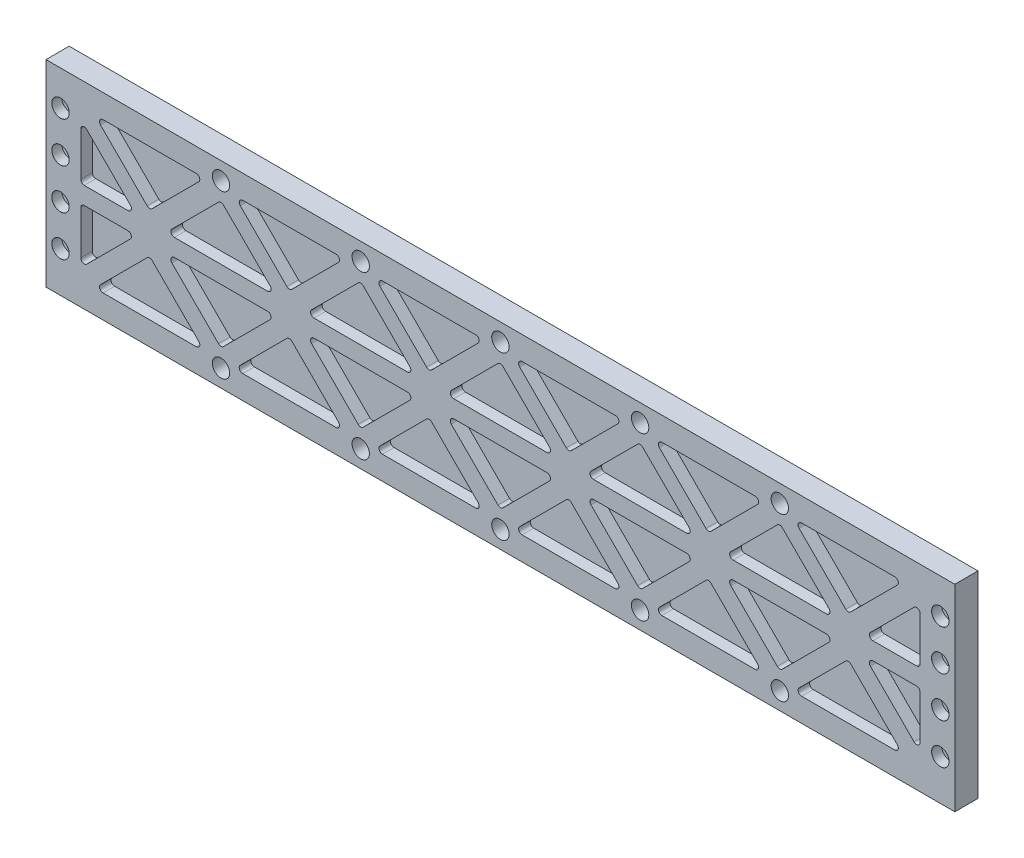
SolidWorks part; units mm, degrees
material "3.3547 (EN-AW 5083)"
ref_plane "Front Plane" through (0, 0, 0) normal (0, 0, 1) x (1, 0, 0)
ref_plane "Top Plane" through (0, 0, 0) normal (0, 1, 0) x (1, 0, 0)
ref_plane "Right Plane" through (0, 0, 0) normal (1, 0, 0) x (0, 0, -1)
sketch "Sketch1" plane through (0, 0, 0) normal (0, 0, 1) x (1, 0, 0)
  line L1 (392, -85) -> (-392, -85)
  line L2 (392, -85) -> (392, 85)
  line L3 (392, 85) -> (-392, 85)
  line L4 (-392, -85) -> (-392, 85)
  line L5 (392, -85) -> (-392, 85) construction
  line L6 (392, 85) -> (-392, -85) construction
  point P0 (0, 0)
  dimension "D1" = 784
  dimension "D2" = 170
extrude "Boss-Extrude1" add sketch "Sketch1" along normal blind 20
sketch "Sketch2" plane through (0, 0, 20) normal (0, 0, 1) x (1, 0, 0)
  line L0 (0, 0) -> (0, 85) construction
  line L1 (392, 85) -> (-392, 85) construction
  line L2 (-40.2574, 7.5) -> (40.2574, 7.5)
  line L3 (42.3787, 12.6213) -> (2.1213, 52.8787)
  line L5 (-2.1213, 52.8787) -> (-42.3787, 12.6213)
  line L7 (392, 0) -> (-392, 0) construction
  line L8 (392, -85) -> (392, 85) construction
  line L9 (-392, 85) -> (-392, -85) construction
  line L11 (-40.2574, -7.5) -> (40.2574, -7.5)
  line L12 (-2.1213, -52.8787) -> (-42.3787, -12.6213)
  line L13 (42.3787, -12.6213) -> (2.1213, -52.8787)
  arc A0 (2.1213, 52.8787) -> (-2.1213, 52.8787) centre (0, 50.7574) ccw
  arc A1 (-42.3787, 12.6213) -> (-40.2574, 7.5) centre (-40.2574, 10.5) ccw
  arc A2 (-40.2574, -7.5) -> (-42.3787, -12.6213) centre (-40.2574, -10.5) ccw
  arc A3 (-2.1213, -52.8787) -> (2.1213, -52.8787) centre (0, -50.7574) ccw
  arc A4 (42.3787, 12.6213) -> (40.2574, 7.5) centre (40.2574, 10.5) cw
  arc A5 (40.2574, -7.5) -> (42.3787, -12.6213) centre (40.2574, -10.5) cw
  point P30 (0, 55)
  point P33 (-47.5, 7.5)
  point P36 (-47.5, -7.5)
  point P39 (0, -55)
  point P42 (47.5, 7.5)
  point P45 (47.5, -7.5)
  dimension "D4" = 3
  dimension "D1" = 45
  dimension "D2" = 15
  dimension "D3" = 30
extrude "Cut-Extrude1" cut sketch "Sketch2" against normal blind 10
sketch "Sketch3" plane through (0, 0, 20) normal (0, 0, 1) x (1, 0, 0)
  line L1 (61.1066, 19.3492) -> (101.364, 59.6066)
  line L2 (99.2426, 64.7279) -> (18.7279, 64.7279)
  line L3 (16.6066, 59.6066) -> (56.864, 19.3492)
  line L7 (58.9853, 0) -> (58.9853, 21.4706) construction
  line L8 (16.6066, -59.6066) -> (56.864, -19.3492)
  line L9 (42.3787, 12.6213) -> (2.1213, 52.8787) construction
  line L10 (2.1213, -52.8787) -> (42.3787, -12.6213) construction
  line L11 (61.1066, -19.3492) -> (101.364, -59.6066)
  line L12 (58.9853, 0) -> (0, 0) construction
  line L13 (99.2426, -64.7279) -> (18.7279, -64.7279)
  line L15 (0, 50.7574) -> (0, 72.2279) construction
  arc A0 (101.364, 59.6066) -> (99.2426, 64.7279) centre (99.2426, 61.7279) ccw
  arc A1 (18.7279, 64.7279) -> (16.6066, 59.6066) centre (18.7279, 61.7279) ccw
  arc A2 (61.1066, 19.3492) -> (56.864, 19.3492) centre (58.9853, 21.4706) cw
  circle A3 centre (58.9853, 0) radius 21.4706 construction
  arc A5 (61.1066, -19.3492) -> (56.864, -19.3492) centre (58.9853, -21.4706) ccw
  arc A6 (18.7279, -64.7279) -> (16.6066, -59.6066) centre (18.7279, -61.7279) cw
  arc A7 (101.364, -59.6066) -> (99.2426, -64.7279) centre (99.2426, -61.7279) cw
  circle A8 centre (0, 72.2279) radius 21.4706 construction
  point P2 (40.2574, 10.5)
  point P13 (106.4853, 64.7279)
  point P16 (11.4853, 64.7279)
  point P22 (18.7279, 61.7279)
  point P25 (0, 50.7574)
  point P38 (106.4853, -64.7279)
  point P40 (0, 50.7574)
  dimension "D2" = 3
  dimension "D1" = 15
extrude "Cut-Extrude2" cut sketch "Sketch3" against normal blind 10
pattern_linear "LPattern1" count 4 spacing 120.52 along (1, 0, 0) count 4 spacing 120.52 along (-1, 0, 0) of "Cut-Extrude1" pattern seed only yes
pattern_linear "LPattern2" count 5 spacing 120.52 along (-1, 0, 0) count 4 spacing 120.52 along (1, 0, 0) of "Cut-Extrude2" pattern seed only yes
sketch "Sketch4" plane through (0, 0, 20) normal (0, 0, 1) x (1, 0, 0)
  line L0 (-392, -85) -> (392, -85) construction
  line L1 (-392, 85) -> (-362, 85)
  line L2 (-392, 85) -> (-392, -85)
  line L3 (-392, -85) -> (-362, -85)
  line L4 (-362, 85) -> (-362, -85)
  dimension "D1" = 30
extrude "Boss-Extrude2" add sketch "Sketch4" against normal up to next (20 mm away)
hole_wizard "CBORE for M8 Hex Socket Head Cap Screw1" positions "Sketch7" profile "Sketch8" counterbore size "M8" standard "DIN" end condition through all
sketch "Sketch7" plane through (0, 0, 20) normal (0, 0, 1) x (1, 0, 0)
  line L0 (-379.5, 85) -> (-379.5, -85) construction
  line L1 (392, 85) -> (-392, 85) construction
  line L2 (-392, -85) -> (392, -85) construction
  line L4 (-392, 85) -> (-392, -85) construction
  point P14 (-379.5, -50)
  point P27 (-379.5, -15)
  point P28 (-379.5, 20)
  point P29 (-379.5, 55)
  dimension "D1" = 12.5
  dimension "D2" = 4
  dimension "D3" = 35
  dimension "D4" = 35
sketch "Sketch8" plane through (-379.5, 55, 20) normal (1, 0, 0) x (0, -1, 0)
  line L0 (0, 0) -> (0, 20)
  line L1 (0, 20) -> (4.5, 20)
  line L3 (4.5, 20) -> (4.5, 8.6)
  line L4 (7.5, 8.6) -> (4.5, 8.6)
  line L5 (7.5, 8.6) -> (7.5, 0.025)
  line L6 (7.5, 0.025) -> (7.525, 0)
  line L7 (7.525, 0) -> (0, 0)
  line L8 (-7.5, 0.025) -> (-7.525, 0) construction
  line L11 (0, -6.35) -> (0, 107.95) construction
  dimension "Thru Hole Dia." = 9
  dimension "Thru Hole Depth" = 20
  dimension "C'Bore Dia." = 15
  dimension "C'Bore Depth" = 8.6
  dimension "Near C'Sink Dia." = 15.05
  dimension "Near C'Sink Angle" = 90
mirror "Mirror2" about plane through (0, 0, 0) normal (1, 0, 0) of "CBORE for M8 Hex Socket Head Cap Screw1", "Boss-Extrude2"
hole_wizard "CBORE for M8 Hex Socket Head Cap Screw2" positions "Sketch9" profile "Sketch11" counterbore size "M8" standard "DIN" end condition up to next
sketch "Sketch9" plane through (0, 0, 20) normal (0, 0, 1) x (1, 0, 0)
  line L0 (-241.04, 7.5) -> (-241.04, 85) construction
  line L1 (-281.2974, 7.5) -> (-200.7826, 7.5) construction
  line L2 (392, 85) -> (-392, 85) construction
  line L3 (0, 0) -> (-392, 0) construction
  line L4 (-392, 85) -> (-392, -85) construction
  point P9 (-241.04, 70)
  point P17 (-241.04, -70)
  dimension "D1" = 15
sketch "Sketch11" plane through (-241.04, -70, 20) normal (1, 0, 0) x (0, -1, 0)
  line L0 (0, 0) -> (0, 20)
  line L1 (0, 20) -> (4.5, 20)
  line L3 (4.5, 20) -> (4.5, 10.6)
  line L4 (4.5, 10.6) -> (7.5, 10.6)
  line L5 (7.5, 10.6) -> (7.5, 0)
  line L7 (7.5, 0) -> (0, 0)
  line L11 (0, -6.35) -> (0, 107.95) construction
  dimension "Thru Hole Dia." = 9
  dimension "Thru Hole Depth" = 20
  dimension "C'Bore Dia." = 15
  dimension "C'Bore Depth" = 10.6
pattern_linear "LPattern3" count 5 spacing 120.52 along (1, 0, 0) of "CBORE for M8 Hex Socket Head Cap Screw2"
fillet "Fillet1" radius 3 8 edges at (362, -53.7249, 15) (362, -7.5, 15) (362, 7.5, 15) (362, 53.7249, 15) (-362, 53.7249, 15) (-362, 7.5, 15) (-362, -7.5, 15) (-362, -53.7249, 15)
